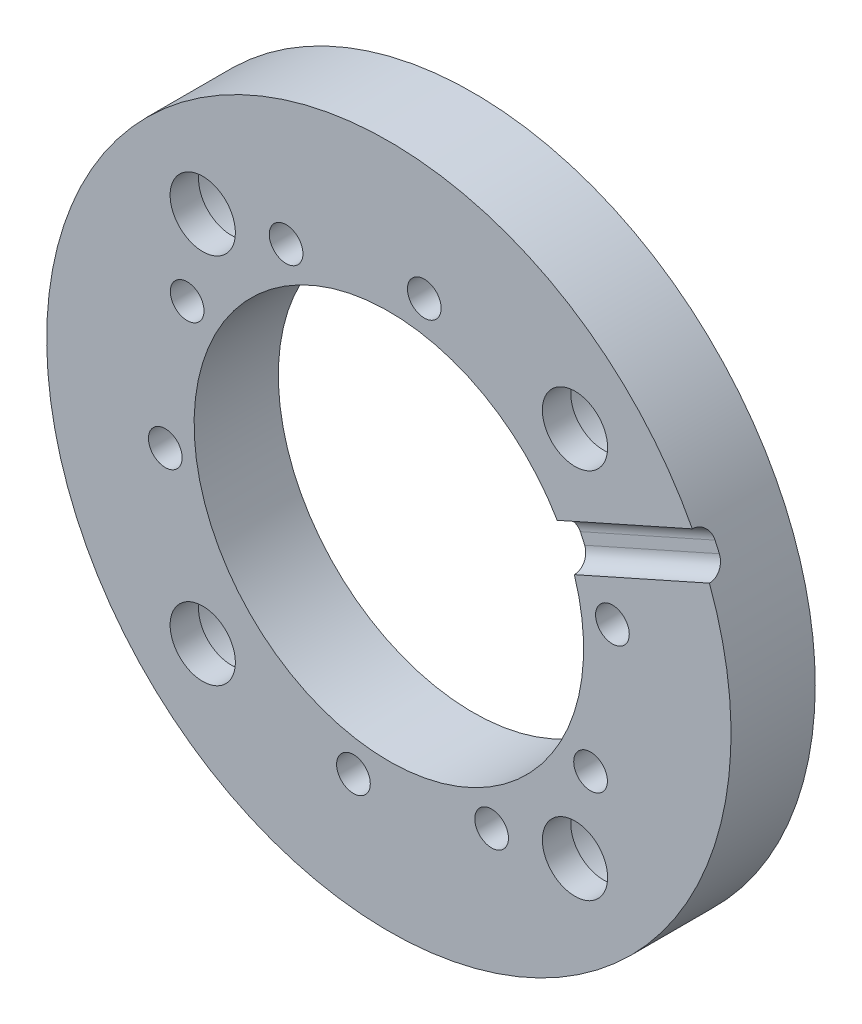
SolidWorks part; units mm, degrees
ref_plane "Front Plane" through (0, 0, 0) normal (0, 0, 1) x (1, 0, 0)
ref_plane "Top Plane" through (0, 0, 0) normal (0, 1, 0) x (1, 0, 0)
ref_plane "Right Plane" through (0, 0, 0) normal (1, 0, 0) x (0, 0, -1)
sketch "Sketch1" plane through (0, 0, 0) normal (0, 0, 1) x (1, 0, 0)
  line L0 (0, 42.6482) -> (0, -42.6482) construction
  line L1 (-40.092, 0) -> (40.092, 0) construction
  line L2 (0, 0) -> (36.9422, 36.9422) construction
  circle A0 centre (0, 0) radius 25 construction
  circle A1 centre (17.6777, 17.6777) radius 3.1
  circle A2 centre (17.6777, -17.6777) radius 3.1
  circle A3 centre (-17.6777, -17.6777) radius 3.1
  circle A4 centre (-17.6777, 17.6777) radius 3.1
  circle A5 centre (0, 0) radius 18.5
  circle A6 centre (0, 0) radius 32.5
  circle A7 centre (17.6777, 17.6777) radius 5.55
  circle A8 centre (-17.6777, 17.6777) radius 5.55
  circle A9 centre (-17.6777, -17.6777) radius 5.55
  circle A10 centre (17.6777, -17.6777) radius 5.55
  dimension "D1" = 50
  dimension "D2" = 6.2
  dimension "D4" = 37
  dimension "D6" = 65
  dimension "D7" = 11.1
  dimension "D8" = 11.1
  dimension "D9" = 11.1
  dimension "D10" = 11.1
  dimension "D5" = 45
  dimension "D3" = 4
extrude "Boss-Extrude2" add sketch "Sketch1" along normal blind 8 contours A6 A10 A5 A9 A8 A7 | A5 A7 A1 | A5 A10 A2 | A5 A9 A3 | A5 A8 A4 region at (-31.5808, 0, 0) region at (12.2846, 17.6777, 0) region at (-23.0707, 17.6777, 0) region at (-23.0707, -17.6777, 0) region at (12.2846, -17.6777, 0)
extrude "Cut-Extrude2" cut sketch "Sketch1<6>" along normal blind 5.3 contours A5 A7 A1 | A5 A10 A2 | A5 A9 A3 | A5 A8 A4 region at (12.2846, 17.6777, 0) region at (-23.0707, 17.6777, 0) region at (-23.0707, -17.6777, 0) region at (12.2846, -17.6777, 0)
sketch "Sketch1<6>" plane through (0, 0, 0) normal (0, 0, 1) x (1, 0, 0) same geometry as "Sketch1"
sketch "Sketch2" plane through (0, 0, 0) normal (0, 0, -1) x (-1, 0, 0)
  line L0 (0, 0) -> (9.7608, 19.1566) construction
  line L1 (17.6777, 17.6777) -> (-17.6777, -17.6777) construction
  circle A0 centre (9.7608, 19.1566) radius 1.6
  circle A1 centre (19.1566, 9.7608) radius 1.6
  circle A2 centre (21.2353, -3.3633) radius 1.6
  circle A4 centre (3.3633, -21.2353) radius 1.6
  circle A5 centre (-9.7608, -19.1566) radius 1.6
  circle A6 centre (-19.1566, -9.7608) radius 1.6
  circle A7 centre (-21.2353, 3.3633) radius 1.6
  circle A9 centre (-3.3633, 21.2353) radius 1.6
  circle A10 centre (-15.2028, 15.2028) radius 1.6 [skipped]
  circle A11 centre (15.2028, -15.2028) radius 1.6 [skipped]
  dimension "D3" = 3.2
  dimension "D1" = 21.5
  dimension "D2" = 18
  dimension "D4" = 10
extrude "Cut-Extrude3" cut sketch "Sketch2" against normal blind 10
ref_plane "Plane1" through (0, 0, 8) normal (0, 0, 1) x (1, 0, 0)
sketch "Sketch4" plane through (0, 0, 8) normal (0, 0, 1) x (1, 0, 0)
  line L0 (0, 0) -> (44.8281, 19.9587) construction
  line L1 (0, -36.2782) -> (0, 36.2782) construction
  line L2 (14.5167, 4.274) -> (32.7876, 12.4087)
  line L3 (14.5167, 4.274) -> (12.8897, 7.9281)
  line L4 (12.8897, 7.9281) -> (31.1606, 16.0629)
  line L5 (32.7876, 12.4087) -> (31.1606, 16.0629)
  dimension "D1" = 4
  dimension "D2" = 20
  dimension "D3" = 2
  dimension "D4" = 15
  dimension "D5" = 66
extrude "Cut-Extrude4" cut sketch "Sketch4" against normal blind 1.5
fillet "Fillet1" radius 1.5 2 edges at (22.4043, 12.1643, 6.5) (24.0312, 8.5101, 6.5)
